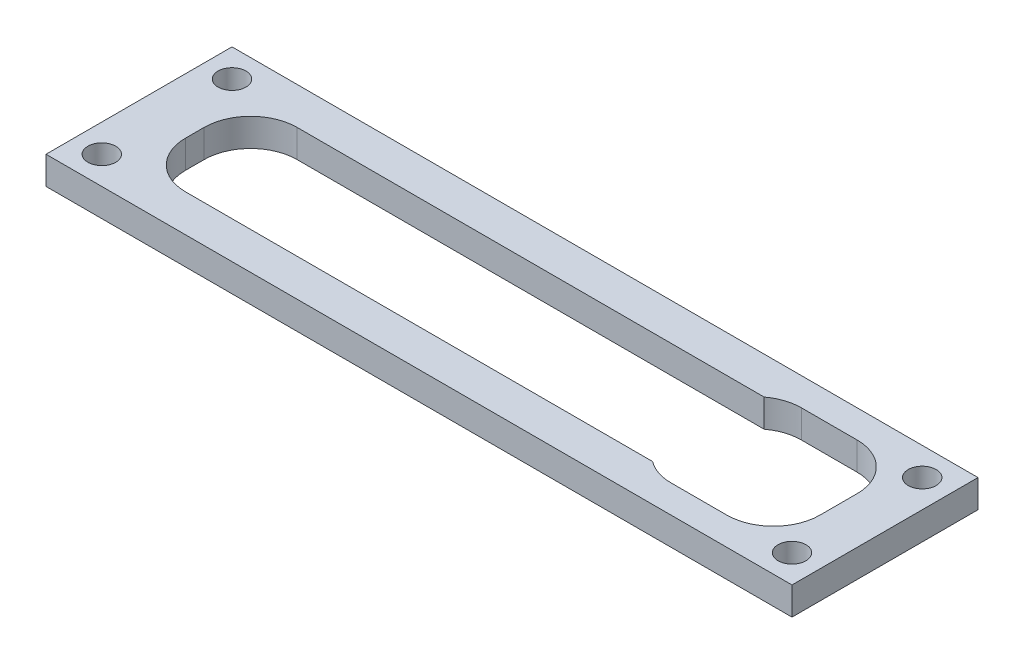
SolidWorks part; units mm, degrees
ref_plane "Front Plane" through (0, 0, 0) normal (0, 0, 1) x (1, 0, 0)
ref_plane "Top Plane" through (0, 0, 0) normal (0, 1, 0) x (1, 0, 0)
ref_plane "Right Plane" through (0, 0, 0) normal (1, 0, 0) x (0, 0, -1)
sketch "Sketch1" plane through (0, 0, 0) normal (0, 1, 0) x (1, 0, 0)
  line L0 (40.107, 20) -> (40.107, 0) construction
  line L1 (0, 0) -> (80.2139, 0)
  line L2 (0, 0) -> (0, 20)
  line L3 (0, 20) -> (80.2139, 20)
  line L4 (80.2139, 0) -> (80.2139, 20)
  line L5 (0, 10) -> (80.2139, 10) construction
  line L6 (40.107, 16) -> (40.107, 4) construction
  line L7 (6, 16) -> (74.2139, 16)
  line L8 (6, 16) -> (6, 4)
  line L9 (6, 4) -> (74.2139, 4)
  line L10 (74.2139, 16) -> (74.2139, 4)
  line L11 (6, 10) -> (74.2139, 10) construction
  circle A0 centre (3, 17) radius 1.5
  circle A1 centre (3, 3) radius 1.5
  circle A2 centre (77.2139, 3) radius 1.5
  circle A3 centre (77.2139, 17) radius 1.5
  point P17 (40.107, 10)
  point P18 (40.107, 10)
  dimension "D7" = 3
  dimension "D1" = 80.2139
  dimension "D2" = 20
  dimension "D3" = 68.2139
  dimension "D4" = 12
  dimension "D5" = 3
  dimension "D6" = 3
extrude "Boss-Extrude1" add sketch "Sketch1" along normal blind 3
sketch "Sketch2" plane through (0, 3, 0) normal (0, 1, 0) x (1, 0, 0)
  line L0 (92, 10) -> (-49908, 10) construction
  line L1 (74.2139, 4) -> (74.2139, 16) construction
  line L2 (61.2139, 17) -> (61.2139, 16)
  line L5 (74.2139, 16) -> (6, 16) construction
  line L6 (68.2139, 17) -> (68.2139, 3) construction
  line L7 (61.2139, 17) -> (75.2139, 17)
  line L9 (61.2139, 3) -> (75.2139, 3)
  line L10 (75.2139, 17) -> (75.2139, 3)
  line L12 (61.2139, 16) -> (74.2139, 16)
  line L13 (74.2139, 16) -> (74.2139, 4)
  line L14 (74.2139, 4) -> (61.2139, 4)
  line L15 (6, 4) -> (74.2139, 4) construction
  line L16 (61.2139, 4) -> (61.2139, 3)
  point P4 (74.2139, 10)
  point P23 (68.2139, 10)
  dimension "D1" = 1
  dimension "D2" = 14
  dimension "D3" = 14
extrude "Cut-Extrude1" cut sketch "Sketch2" against normal through all
fillet "Fillet1" radius 5 6 edges at (75.2139, 1.5, -17) (75.2139, 1.5, -3) (61.2139, 1.5, -17) (61.2139, 1.5, -3) (6, 1.5, -4) (6, 1.5, -16)
equation "\"TrackLength\"= ( ( \"n\" * 28 ) ) / cos ( \"MountAngle\" ) - ( 2 * \"x\" )"
equation "\"D1@Sketch1\"=\"TrackLength\""
equation "\"TrackWidth\"= \"MarbleTrackWidth\" + ( 2 * 4 )"
equation "\"D2@Sketch1\"=\"TrackWidth\""
equation "\"MarbleTrackWidth\"= \"MarbleWidth\" - 1"
equation "\"MarbleTrackLength\"= \"TrackLength\" - ( 2 * 6 )"
equation "\"D3@Sketch1\"=\"MarbleTrackLength\""
equation "\"D4@Sketch1\"=\"MarbleTrackWidth\""
equation "\"MarbleWidth\"= 13"
equation "\"n\"= 3"
equation "\"MountAngle\"= 5"
equation "\"x\"= 14 / cos ( \"MountAngle\" ) - 12"
